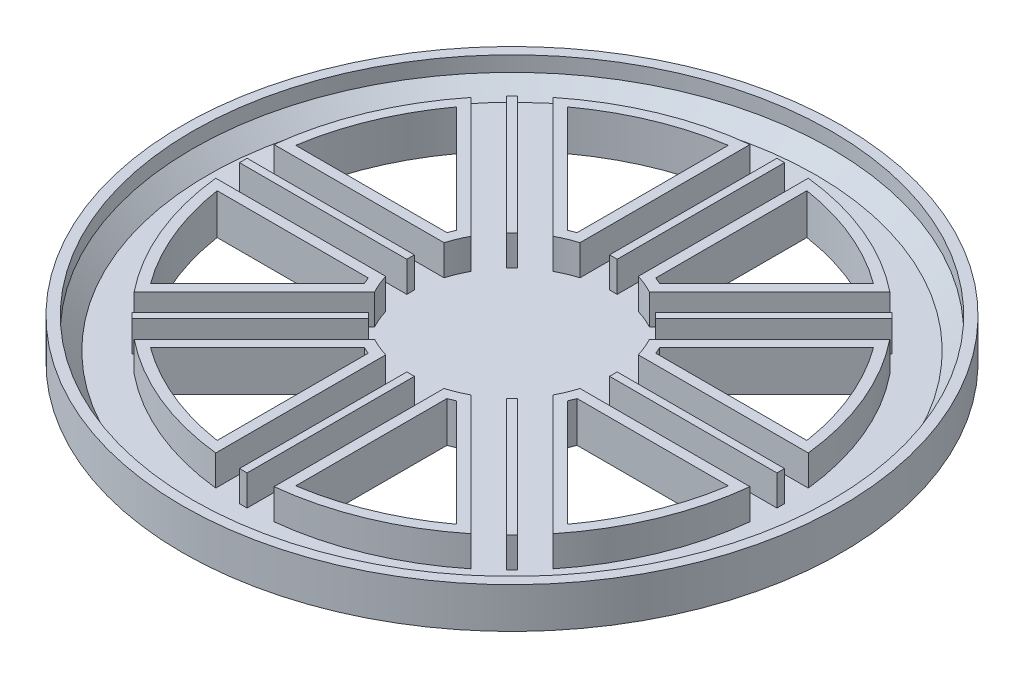
SolidWorks part; units mm, degrees
ref_plane "Plan de face" through (0, 0, 0) normal (0, 0, 1) x (1, 0, 0)
ref_plane "Plan de dessus" through (0, 0, 0) normal (0, 1, 0) x (1, 0, 0)
ref_plane "Plan de droite" through (0, 0, 0) normal (1, 0, 0) x (0, 0, -1)
sketch "Esquisse1" plane through (0, 0, 0) normal (0, 1, 0) x (1, 0, 0)
  circle A0 centre (0, 0) radius 65
  dimension "D1" = 130
extrude "Boss.-Extru.1" add sketch "Esquisse1" along normal blind 8
sketch "Esquisse2" plane through (0, 8, 0) normal (0, 1, 0) x (1, 0, 0)
  circle A0 centre (0, 0) radius 63
  circle A1 centre (0, 0) radius 65 construction
  dimension "D1" = 2
extrude "Enlèv. mat.-Extru.1" cut sketch "Esquisse2" against normal offset from surface (6 mm away) 2 up to face at (0, 0, 65)
sketch "Esquisse3" plane through (0, 2, 0) normal (0, 1, 0) x (1, 0, 0)
  line L0 (0, 0) -> (-63, 0) construction
  line L1 (0, 0) -> (-44.5477, -44.5477) construction
  line L2 (-41.3213, -33.1896) -> (-17.6109, -9.4792)
  line L3 (-19.1556, -5.75) -> (-52.6872, -5.75)
  line L4 (-48.9656, -20.2822) -> (0, 0) construction
  line L5 (-36.9426, -38.0032) -> (-13.6019, -14.6625)
  line L6 (-38.0032, -36.9426) -> (-14.6625, -13.6019)
  circle A0 centre (0, 0) radius 63 construction
  arc A1 (-17.6109, -9.4792) -> (-19.1556, -5.75) centre (0, 0) cw
  arc A2 (-52.6872, -5.75) -> (-41.3213, -33.1896) centre (0, 0) ccw
  arc A3 (-14.6625, -13.6019) -> (-13.6019, -14.6625) centre (0, 0) ccw
  arc A4 (-38.0032, -36.9426) -> (-36.9426, -38.0032) centre (0, 0) ccw
  point P12 (-18.4776, -7.6537)
  point P20 (-14.1421, -14.1421)
  point P21 (-37.4767, -37.4767)
  dimension "D3" = 20
  dimension "D4" = 10
  dimension "D1" = 45
  dimension "D2" = 5
  dimension "D5" = 1.5
extrude "Boss.-Extru.2" add sketch "Esquisse3" along normal up to surface (6 mm away) up to face at (0, 8, 63)
pattern_circular "Répétition circulaire1" count 8 over 360 about axis through (0, 52.534, 0) along (0, -1, 0) of "Boss.-Extru.2" reverse direction yes
shell "Coque1" thickness 2 removed face at (0, 0, 65) removed face at (33.2077, 8, -13.7551) removed face at (33.2077, 8, 13.7551) removed face at (13.7551, 8, 33.2077) removed face at (-13.7551, 8, 33.2077) removed face at (-33.2077, 8, 13.7551) removed face at (-33.2077, 8, -13.7551) removed face at (-13.7551, 8, -33.2077) removed face at (13.7551, 8, -33.2077)
sketch "Esquisse4" plane through (0, 0, 0) normal (0, 0, 1) x (1, 0, 0)
  line L0 (-65, 8) -> (-2, 117.1192)
  line L1 (-2, 117.1192) -> (-2, 113.6551)
  line L2 (-2, 113.6551) -> (-63, 8)
  line L3 (-63, 8) -> (-63, 2) construction
  line L4 (-63, 8) -> (-65, 8)
  line L5 (63, 8) -> (-63, 8) construction
  line L6 (-52.9947, 8) -> (-19.9859, 8) construction
  dimension "D1" = 2
  dimension "D2" = 60
extrude "Boss.-Extru.3" [suppressed] add sketch "Esquisse4" along normal mid plane 4
pattern_circular "Répétition circulaire2" [suppressed] count 3 over 360 of bodies 105
chamfer "Chamfer1" distance 3 angle 45 1 edges at (0, 2, 63)
